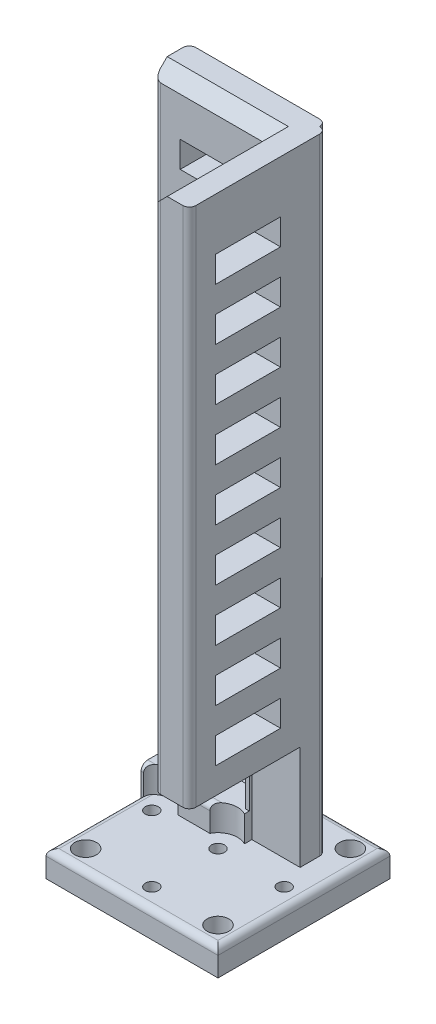
SolidWorks part; units mm, degrees
ref_plane "Front Plane" through (0, 0, 0) normal (0, 0, 1) x (1, 0, 0)
ref_plane "Top Plane" through (0, 0, 0) normal (0, 1, 0) x (1, 0, 0)
ref_plane "Right Plane" through (0, 0, 0) normal (1, 0, 0) x (0, 0, -1)
sketch "Sketch3" plane through (0, 0, 0) normal (0, 1, 0) x (1, 0, 0)
  line L0 (24, 0) -> (0, 0) construction
  line L1 (0, 0) -> (24, 0) construction
  line L2 (0, 0) -> (0, -36)
  line L3 (0, -36) -> (24, -36)
  line L4 (24, 0) -> (24, -36)
  line L5 (0, 0) -> (-36, 0)
  line L6 (24, 0) -> (24, 24)
  line L7 (24, 24) -> (-36, 24)
  line L8 (-36, 0) -> (-36, 24)
  dimension "D1" = 24
  dimension "D2" = 24
  dimension "D3" = 60
  dimension "D4" = 36
extrude "Boss-Extrude2" add sketch "Sketch3" along normal blind 250
sketch "Sketch4" plane through (0, 0, 0) normal (0, -1, 0) x (1, 0, 0)
  line L0 (-36, -24) -> (-36, 0) construction
  line L1 (0, 0) -> (-36, 0)
  line L2 (0, 0) -> (0, 36)
  line L3 (0, 36) -> (-36, 36)
  line L4 (-36, 0) -> (-36, 36)
  line L5 (-36, -24) -> (24, -24)
  line L6 (-36, -24) -> (-36, -40)
  line L7 (-36, -40) -> (40, -40)
  line L8 (40, -24) -> (40, -40)
  line L9 (24, 36) -> (40, 36)
  line L10 (24, 36) -> (24, -24)
  line L11 (24, -24) -> (40, -24) construction
  line L12 (40, 36) -> (40, -24)
  line L13 (0, 36) -> (24, 36) construction
  line L14 (24, -24) -> (40, -24) construction
  line L15 (-36, 18.4) -> (0, 18.4) construction
  line L16 (-18.4, 36) -> (-18.4, 0) construction
  line L17 (-36, -32.4) -> (40, -32.4) construction
  line L18 (32.4, 36) -> (32.4, -40) construction
  line L19 (-36, -7) -> (40, -7) construction
  line L20 (-18.4, 0) -> (-18.4, -40) construction
  line L21 (7, -40) -> (7, 36) construction
  circle A0 centre (-18.4, 18.4) radius 4.15
  circle A1 centre (-18.4, -32.4) radius 4.15
  circle A2 centre (32.4, 18.4) radius 4.15
  circle A3 centre (32.4, -32.4) radius 4.15
  circle A5 centre (-18.4, -7) radius 2.5
  circle A6 centre (32.4, -7) radius 2.5
  circle A7 centre (7, -32.4) radius 2.5
  dimension "D3" = 8.3
  dimension "D4" = 8.3
  dimension "D1" = 8.3
  dimension "D7" = 8.3
  dimension "D11" = 5
  dimension "D12" = 5
  dimension "D14" = 5
  dimension "D5" = 50.8
  dimension "D6" = 16
  dimension "D9" = 50.8
  dimension "D8" = 50.8
  dimension "D10" = 25.4
  dimension "D13" = 25.4
  dimension "D15" = 8.4
  dimension "D16" = 17.6
  dimension "D17" = 25.4
  dimension "D18" = 25.4
  dimension "D19" = 25.4
  dimension "D21" = 17.6
  dimension "D20" = 7.6
  dimension "D22" = 7.6
extrude "Boss-Extrude3" add sketch "Sketch4" against normal blind 10
sketch "Sketch5" plane through (0, 0, 0) normal (0, 0, 1) x (1, 0, 0)
  line L0 (-36, 250) -> (-36, 10) construction
  line L1 (-16, 30) -> (9, 30)
  line L2 (-16, 30) -> (-16, 20)
  line L3 (-16, 20) -> (9, 20)
  line L4 (9, 30) -> (9, 20)
  line L9 (-36, 10) -> (0, 10) construction
  line L10 (-16, 50) -> (-16, 40)
  line L11 (-16, 50) -> (9, 50)
  line L12 (9, 50) -> (9, 40)
  line L13 (-16, 40) -> (9, 40)
  line L14 (-16, 70) -> (-16, 60)
  line L15 (-16, 70) -> (9, 70)
  line L16 (9, 70) -> (9, 60)
  line L17 (-16, 60) -> (9, 60)
  line L18 (-16, 90) -> (-16, 80)
  line L19 (-16, 90) -> (9, 90)
  line L20 (9, 90) -> (9, 80)
  line L21 (-16, 80) -> (9, 80)
  line L22 (-16, 110) -> (-16, 100)
  line L23 (-16, 110) -> (9, 110)
  line L24 (9, 110) -> (9, 100)
  line L25 (-16, 100) -> (9, 100)
  line L26 (-16, 130) -> (-16, 120)
  line L27 (-16, 130) -> (9, 130)
  line L28 (9, 130) -> (9, 120)
  line L29 (-16, 120) -> (9, 120)
  line L30 (-16, 150) -> (-16, 140)
  line L31 (-16, 150) -> (9, 150)
  line L32 (9, 150) -> (9, 140)
  line L33 (-16, 140) -> (9, 140)
  line L34 (-16, 170) -> (-16, 160)
  line L35 (-16, 170) -> (9, 170)
  line L36 (9, 170) -> (9, 160)
  line L37 (-16, 160) -> (9, 160)
  line L38 (-16, 190) -> (-16, 180)
  line L39 (-16, 190) -> (9, 190)
  line L40 (9, 190) -> (9, 180)
  line L41 (-16, 180) -> (9, 180)
  line L42 (-16, 210) -> (-16, 200)
  line L43 (-16, 210) -> (9, 210)
  line L44 (9, 210) -> (9, 200)
  line L45 (-16, 200) -> (9, 200)
  line L46 (-16, 230) -> (-16, 220)
  line L47 (-16, 230) -> (9, 230)
  line L48 (9, 230) -> (9, 220)
  line L49 (-16, 220) -> (9, 220)
  dimension "D1" = 10
  dimension "D2" = 25
  dimension "D3" = 20
  dimension "D4" = 10
  dimension "D6" = 10
  dimension "D5" = 11
extrude "Cut-Extrude1" cut sketch "Sketch5" against normal up to surface (24 mm away) up to face at (-6, 130, -24)
sketch "Sketch6" plane through (0, 0, 0) normal (-1, 0, 0) x (0, 0, 1)
  line L0 (0, 10) -> (36, 10) construction
  line L1 (-9, 20) -> (16, 20)
  line L2 (-9, 20) -> (-9, 30)
  line L3 (-9, 30) -> (16, 30)
  line L4 (16, 20) -> (16, 30)
  line L5 (36, 250) -> (36, 10) construction
  line L38 (16, 40) -> (16, 50)
  line L39 (-9, 40) -> (-9, 50)
  line L40 (-9, 40) -> (16, 40)
  line L41 (-9, 50) -> (16, 50)
  line L42 (16, 60) -> (16, 70)
  line L43 (-9, 60) -> (-9, 70)
  line L44 (-9, 60) -> (16, 60)
  line L45 (-9, 70) -> (16, 70)
  line L46 (16, 80) -> (16, 90)
  line L47 (-9, 80) -> (-9, 90)
  line L48 (-9, 80) -> (16, 80)
  line L49 (-9, 90) -> (16, 90)
  line L50 (16, 100) -> (16, 110)
  line L51 (-9, 100) -> (-9, 110)
  line L52 (-9, 100) -> (16, 100)
  line L53 (-9, 110) -> (16, 110)
  line L54 (16, 120) -> (16, 130)
  line L55 (-9, 120) -> (-9, 130)
  line L56 (-9, 120) -> (16, 120)
  line L57 (-9, 130) -> (16, 130)
  line L58 (16, 140) -> (16, 150)
  line L59 (-9, 140) -> (-9, 150)
  line L60 (-9, 140) -> (16, 140)
  line L61 (-9, 150) -> (16, 150)
  line L62 (16, 160) -> (16, 170)
  line L63 (-9, 160) -> (-9, 170)
  line L64 (-9, 160) -> (16, 160)
  line L65 (-9, 170) -> (16, 170)
  line L66 (16, 180) -> (16, 190)
  line L67 (-9, 180) -> (-9, 190)
  line L68 (-9, 180) -> (16, 180)
  line L69 (-9, 190) -> (16, 190)
  line L70 (16, 200) -> (16, 210)
  line L71 (-9, 200) -> (-9, 210)
  line L72 (-9, 200) -> (16, 200)
  line L73 (-9, 210) -> (16, 210)
  line L74 (16, 220) -> (16, 230)
  line L75 (-9, 220) -> (-9, 230)
  line L76 (-9, 220) -> (16, 220)
  line L77 (-9, 230) -> (16, 230)
  dimension "D1" = 10
  dimension "D2" = 10
  dimension "D3" = 25
  dimension "D4" = 20
  dimension "D6" = 10
  dimension "D5" = 11
extrude "Cut-Extrude2" cut sketch "Sketch6" against normal up to surface (24 mm away) up to face at (24, 130, 6)
sketch "Sketch7" plane through (0, 250, 0) normal (0, 1, 0) x (1, 0, 0)
  line L0 (0, 0) -> (0, -36) construction
  line L1 (-36, 0) -> (0, 0)
  line L2 (-36, 0) -> (-36, 15.5)
  line L3 (-36, 15.5) -> (15.5, 15.5)
  line L4 (15.5, 0) -> (15.5, 15.5)
  line L5 (0, 0) -> (15.5, 0) construction
  line L6 (15.5, 0) -> (0, 0) construction
  line L7 (15.5, 0) -> (15.5, -36)
  line L8 (15.5, -36) -> (0, -36)
  line L9 (0, 0) -> (0, -36)
  dimension "D1" = 15.5
  dimension "D2" = 15.5
extrude "Cut-Extrude3" cut sketch "Sketch7" against normal up to surface (240 mm away) up to face at (-18.4, 10, 14.25)
sketch "Sketch8" plane through (0, 10, 0) normal (0, 1, 0) x (1, 0, 0)
  line L0 (14, 24) -> (14, 29)
  line L1 (24, 24) -> (-36, 24) construction
  line L2 (14, 29) -> (26.5, 29)
  line L3 (29, 26.5) -> (29, 14)
  line L4 (29, 14) -> (24, 14)
  line L5 (24, -36) -> (24, 24) construction
  line L6 (24, 14) -> (24, 24)
  line L7 (24, 24) -> (-36, 24) construction
  line L8 (24, 24) -> (14, 24)
  line L9 (26.5, 29) -> (29, 29) construction
  line L10 (29, 29) -> (26.5, 29) construction
  line L11 (29, 29) -> (29, 26.5) construction
  line L12 (29, 26.5) -> (26.5, 26.5)
  line L13 (26.5, 29) -> (26.5, 26.5)
  line L14 (29, 29) -> (29, 26.5) construction
  dimension "D1" = 5
  dimension "D2" = 5
  dimension "D3" = 10
  dimension "D4" = 10
  dimension "D5" = 2.5
  dimension "D6" = 2.5
extrude "Boss-Extrude4" add sketch "Sketch8" along normal up to surface (240 mm away) up to face at (1.1667, 250, -1.1667)
ref_plane "Plane1" through (0, 40, 0) normal (0, 1, 0) x (1, 0, 0)
sketch "Sketch10" plane through (24, 0, 0) normal (1, 0, 0) x (0, 0, -1)
  line L0 (-36, 250) -> (14, 250)
  line L1 (14, 250) -> (14, 20)
  line L2 (14, 10) -> (-36, 10) construction
  line L3 (-36, 20) -> (-36, 250)
  line L4 (9, 30) -> (-16, 30)
  line L5 (9, 20) -> (9, 30)
  line L6 (-16, 20) -> (9, 20)
  line L7 (-16, 30) -> (-16, 20)
  line L8 (9, 30) -> (-16, 30)
  line L9 (9, 20) -> (9, 30)
  line L11 (-16, 30) -> (-16, 20)
  line L12 (9, 40) -> (9, 50)
  line L13 (-16, 40) -> (9, 40)
  line L14 (-16, 50) -> (-16, 40)
  line L15 (9, 50) -> (-16, 50)
  line L16 (9, 40) -> (9, 50)
  line L17 (-16, 40) -> (9, 40)
  line L18 (-16, 50) -> (-16, 40)
  line L19 (9, 50) -> (-16, 50)
  line L20 (9, 60) -> (9, 70)
  line L21 (-16, 60) -> (9, 60)
  line L22 (-16, 70) -> (-16, 60)
  line L23 (9, 70) -> (-16, 70)
  line L24 (9, 60) -> (9, 70)
  line L25 (-16, 60) -> (9, 60)
  line L26 (-16, 70) -> (-16, 60)
  line L27 (9, 70) -> (-16, 70)
  line L28 (9, 120) -> (9, 130)
  line L29 (-16, 120) -> (9, 120)
  line L30 (-16, 130) -> (-16, 120)
  line L31 (9, 130) -> (-16, 130)
  line L32 (9, 120) -> (9, 130)
  line L33 (-16, 120) -> (9, 120)
  line L34 (-16, 130) -> (-16, 120)
  line L35 (9, 130) -> (-16, 130)
  line L36 (9, 100) -> (9, 110)
  line L37 (-16, 100) -> (9, 100)
  line L38 (-16, 110) -> (-16, 100)
  line L39 (9, 110) -> (-16, 110)
  line L40 (9, 100) -> (9, 110)
  line L41 (-16, 100) -> (9, 100)
  line L42 (-16, 110) -> (-16, 100)
  line L43 (9, 110) -> (-16, 110)
  line L44 (9, 80) -> (9, 90)
  line L45 (-16, 80) -> (9, 80)
  line L46 (-16, 90) -> (-16, 80)
  line L47 (9, 90) -> (-16, 90)
  line L48 (9, 80) -> (9, 90)
  line L49 (-16, 80) -> (9, 80)
  line L50 (-16, 90) -> (-16, 80)
  line L51 (9, 90) -> (-16, 90)
  line L52 (9, 220) -> (9, 230)
  line L53 (-16, 220) -> (9, 220)
  line L54 (-16, 230) -> (-16, 220)
  line L55 (9, 230) -> (-16, 230)
  line L56 (9, 220) -> (9, 230)
  line L57 (-16, 220) -> (9, 220)
  line L58 (-16, 230) -> (-16, 220)
  line L59 (9, 230) -> (-16, 230)
  line L60 (9, 200) -> (9, 210)
  line L61 (-16, 200) -> (9, 200)
  line L62 (-16, 210) -> (-16, 200)
  line L63 (9, 210) -> (-16, 210)
  line L64 (9, 200) -> (9, 210)
  line L65 (-16, 200) -> (9, 200)
  line L66 (-16, 210) -> (-16, 200)
  line L67 (9, 210) -> (-16, 210)
  line L68 (9, 180) -> (9, 190)
  line L69 (-16, 180) -> (9, 180)
  line L70 (-16, 190) -> (-16, 180)
  line L71 (9, 190) -> (-16, 190)
  line L72 (9, 180) -> (9, 190)
  line L73 (-16, 180) -> (9, 180)
  line L74 (-16, 190) -> (-16, 180)
  line L75 (9, 190) -> (-16, 190)
  line L76 (9, 160) -> (9, 170)
  line L77 (-16, 160) -> (9, 160)
  line L78 (-16, 170) -> (-16, 160)
  line L79 (9, 170) -> (-16, 170)
  line L80 (9, 160) -> (9, 170)
  line L81 (-16, 160) -> (9, 160)
  line L82 (-16, 170) -> (-16, 160)
  line L83 (9, 170) -> (-16, 170)
  line L84 (9, 140) -> (9, 150)
  line L85 (-16, 140) -> (9, 140)
  line L86 (-16, 150) -> (-16, 140)
  line L87 (9, 150) -> (-16, 150)
  line L88 (9, 140) -> (9, 150)
  line L89 (-16, 140) -> (9, 140)
  line L90 (-16, 150) -> (-16, 140)
  line L91 (9, 150) -> (-16, 150)
  line L92 (-16, 20) -> (-36, 20)
  line L93 (9, 20) -> (14, 20)
  line L94 (-36, 10) -> (-36, 20) construction
  line L95 (14, 20) -> (14, 10) construction
  dimension "D1" = 0
  dimension "D2" = 0
  dimension "D3" = 0
  dimension "D4" = 0
  dimension "D5" = 0
  dimension "D6" = 0
  dimension "D7" = 0
  dimension "D8" = 0
  dimension "D9" = 0
  dimension "D10" = 0
  dimension "D11" = 0
extrude "Boss-Extrude8" add sketch "Sketch10" along normal blind 5
sketch "Sketch11" plane through (0, 0, -24) normal (0, 0, -1) x (-1, 0, 0)
  line L0 (-9, 20) -> (-14, 20)
  line L1 (-14, 250) -> (-14, 10) construction
  line L2 (16, 20) -> (36, 20)
  line L3 (36, 250) -> (36, 10) construction
  line L4 (-9, 230) -> (-9, 220)
  line L5 (16, 230) -> (-9, 230)
  line L6 (16, 220) -> (16, 230)
  line L7 (-9, 220) -> (16, 220)
  line L8 (-9, 230) -> (-9, 220)
  line L9 (16, 230) -> (-9, 230)
  line L10 (16, 220) -> (16, 230)
  line L11 (-9, 220) -> (16, 220)
  line L12 (-9, 210) -> (-9, 200)
  line L13 (16, 210) -> (-9, 210)
  line L14 (16, 200) -> (16, 210)
  line L15 (-9, 200) -> (16, 200)
  line L16 (-9, 210) -> (-9, 200)
  line L17 (16, 210) -> (-9, 210)
  line L18 (16, 200) -> (16, 210)
  line L19 (-9, 200) -> (16, 200)
  line L20 (-9, 190) -> (-9, 180)
  line L21 (16, 190) -> (-9, 190)
  line L22 (16, 180) -> (16, 190)
  line L23 (-9, 180) -> (16, 180)
  line L24 (-9, 190) -> (-9, 180)
  line L25 (16, 190) -> (-9, 190)
  line L26 (16, 180) -> (16, 190)
  line L27 (-9, 180) -> (16, 180)
  line L28 (-9, 170) -> (-9, 160)
  line L29 (16, 170) -> (-9, 170)
  line L30 (16, 160) -> (16, 170)
  line L31 (-9, 160) -> (16, 160)
  line L32 (-9, 170) -> (-9, 160)
  line L33 (16, 170) -> (-9, 170)
  line L34 (16, 160) -> (16, 170)
  line L35 (-9, 160) -> (16, 160)
  line L36 (-9, 150) -> (-9, 140)
  line L37 (16, 150) -> (-9, 150)
  line L38 (16, 140) -> (16, 150)
  line L39 (-9, 140) -> (16, 140)
  line L40 (-9, 150) -> (-9, 140)
  line L41 (16, 150) -> (-9, 150)
  line L42 (16, 140) -> (16, 150)
  line L43 (-9, 140) -> (16, 140)
  line L44 (-9, 130) -> (-9, 120)
  line L45 (16, 130) -> (-9, 130)
  line L46 (16, 120) -> (16, 130)
  line L47 (-9, 120) -> (16, 120)
  line L48 (-9, 130) -> (-9, 120)
  line L49 (16, 130) -> (-9, 130)
  line L50 (16, 120) -> (16, 130)
  line L51 (-9, 120) -> (16, 120)
  line L52 (-9, 110) -> (-9, 100)
  line L53 (16, 110) -> (-9, 110)
  line L54 (16, 100) -> (16, 110)
  line L55 (-9, 100) -> (16, 100)
  line L56 (-9, 110) -> (-9, 100)
  line L57 (16, 110) -> (-9, 110)
  line L58 (16, 100) -> (16, 110)
  line L59 (-9, 100) -> (16, 100)
  line L60 (-9, 90) -> (-9, 80)
  line L61 (16, 90) -> (-9, 90)
  line L62 (16, 80) -> (16, 90)
  line L63 (-9, 80) -> (16, 80)
  line L64 (-9, 90) -> (-9, 80)
  line L65 (16, 90) -> (-9, 90)
  line L66 (16, 80) -> (16, 90)
  line L67 (-9, 80) -> (16, 80)
  line L68 (-9, 70) -> (-9, 60)
  line L69 (16, 70) -> (-9, 70)
  line L70 (16, 60) -> (16, 70)
  line L71 (-9, 60) -> (16, 60)
  line L72 (-9, 70) -> (-9, 60)
  line L73 (16, 70) -> (-9, 70)
  line L74 (16, 60) -> (16, 70)
  line L75 (-9, 60) -> (16, 60)
  line L76 (-9, 50) -> (-9, 40)
  line L77 (16, 50) -> (-9, 50)
  line L78 (16, 40) -> (16, 50)
  line L79 (-9, 40) -> (16, 40)
  line L80 (-9, 50) -> (-9, 40)
  line L81 (16, 50) -> (-9, 50)
  line L82 (16, 40) -> (16, 50)
  line L83 (-9, 40) -> (16, 40)
  line L84 (16, 30) -> (-9, 30)
  line L85 (16, 20) -> (16, 30)
  line L86 (-9, 20) -> (16, 20)
  line L87 (-9, 30) -> (-9, 20)
  line L88 (16, 30) -> (-9, 30)
  line L89 (16, 20) -> (16, 30)
  line L90 (-9, 20) -> (16, 20) construction
  line L91 (-9, 30) -> (-9, 20)
  line L92 (36, 20) -> (36, 250)
  line L93 (36, 250) -> (-14, 250)
  line L94 (-14, 250) -> (-14, 20)
  dimension "D1" = 0
  dimension "D2" = 0
  dimension "D3" = 0
  dimension "D4" = 0
  dimension "D5" = 0
  dimension "D6" = 0
  dimension "D7" = 0
  dimension "D8" = 0
  dimension "D9" = 0
  dimension "D10" = 0
  dimension "D11" = 0
extrude "Boss-Extrude9" add sketch "Sketch11" along normal blind 5
sketch "Sketch12" plane through (0, 10, 0) normal (0, 1, 0) x (1, 0, 0)
  line L0 (-36, -36) -> (-36, 15.5) construction
  line L1 (-36, 10.5) -> (10.5, 10.5)
  line L2 (-36, 10.5) -> (-36, 15.5)
  line L3 (-36, 15.5) -> (15.5, 15.5)
  line L4 (15.5, 10.5) -> (15.5, 15.5)
  line L5 (15.5, -36) -> (-36, -36) construction
  line L6 (10.5, -36) -> (15.5, -36)
  line L7 (10.5, -36) -> (10.5, 10.5)
  line L8 (10.5, 10.5) -> (15.5, 10.5) construction
  line L9 (15.5, -36) -> (15.5, 10.5)
  line L10 (10.5, 10.5) -> (15.5, 10.5) construction
  dimension "D1" = 5
  dimension "D2" = 5
extrude "Boss-Extrude10" add sketch "Sketch12" along normal up to surface (10 mm away) up to face at (-3.5, 20, -19.75)
sketch "Sketch13" plane through (0, 0, 0) normal (0, -1, 0) x (1, 0, 0)
  line L0 (-36, 18.4) -> (40, 18.4) construction
  line L1 (-36, -40) -> (-36, 36) construction
  line L2 (40, -40) -> (40, 36) construction
  line L3 (-18.4, -40) -> (-18.4, 36) construction
  line L4 (-36, -40) -> (40, -40) construction
  line L5 (-36, 36) -> (40, 36) construction
  circle A0 centre (7, 18.4) radius 2.5
  circle A1 centre (32.4, -7) radius 2.5 construction
  circle A3 centre (-18.4, -7) radius 2.5
  circle A4 centre (-18.4, -32.4) radius 4.15 construction
  circle A5 centre (7, -32.4) radius 2.5 construction
  circle A6 centre (7, -7) radius 2.5
  dimension "D1" = 25.4
  dimension "D2" = 25.4
  dimension "D3" = 25.4
  dimension "D4" = 25.4
  dimension "D5" = 25.4
  dimension "D6" = 25.4
extrude "Cut-Extrude4" cut sketch "Sketch13" against normal up to surface (20 mm away) up to face at (3.2143, 20, -3.2143)
sketch "Sketch14" plane through (0, 20, 0) normal (0, 1, 0) x (1, 0, 0)
  circle A0 centre (-18.4, 7) radius 7.5
  circle A1 centre (7, 7) radius 7.5
  circle A2 centre (7, -18.4) radius 7.5
  dimension "D1" = 15
extrude "Cut-Extrude5" cut sketch "Sketch14" against normal up to surface (10 mm away) up to face at (7, 10, 15.9)
sketch "Sketch15" plane through (0, 250, 0) normal (0, 1, 0) x (1, 0, 0)
  line L0 (10.5, -36) -> (-36, -36) construction
  line L1 (-36, 40) -> (-26, 40)
  line L2 (-36, 40) -> (-36, -36)
  line L3 (-36, -36) -> (-26, -36)
  line L4 (-26, 40) -> (-26, -26)
  line L5 (-26, -26) -> (-26, -36) construction
  line L6 (40, -36) -> (-26, -36)
  line L7 (40, -36) -> (40, -26)
  line L8 (40, -26) -> (-26, -26)
  line L9 (-26, -36) -> (-26, -26) construction
  dimension "D1" = 10
  dimension "D2" = 10
extrude "Cut-Extrude6" cut sketch "Sketch15" against normal up to surface (250 mm away) up to face at (7, 0, 15.9)
chamfer "Chamfer3" distance 5 angle 45 2 edges at (15.5, 250, 5.25) (-5.25, 250, -15.5)
fillet "Fillet1" radius 2.5 24 edges at (40, 10, -7) (7, 10, -40) (10.5, 20, 25.5166) (-21, 20, -29) (11.5, 20, -29) (29, 20, -11.5) (29, 20, 21) (26.5, 130, -29) (29, 130, -26.5) (10.5, 20, 5.7) (-5.7, 20, -10.5) (-25.5166, 20, -10.5) (14, 15, -29) (29, 15, -14) (15.5, 132.5, 26) (29, 135, 26) (24, 15, 26) (-26, 15, -24) (-26, 135, -29) (-26, 132.5, -15.5) (-26, 10, -32) (32, 10, 26) (-7.75, 10, 26) (-26, 10, 7.75)
sketch "Sketch16" plane through (29, 0, 0) normal (1, 0, 0) x (0, 0, -1)
  line L0 (16.5, 22.5) -> (16.5, 10) construction
  line L1 (16.5, 10) -> (-26, 10)
  line L2 (16.5, 10) -> (16.5, 50)
  line L3 (16.5, 50) -> (-26, 50)
  line L4 (-26, 10) -> (-26, 50)
  line L5 (-26, 20) -> (-26, 250) construction
  line L7 (9, 50) -> (-16, 50) construction
  line L8 (-23.5, 10) -> (14, 10) construction
extrude "Cut-Extrude7" cut sketch "Sketch16" against normal up to surface (18.5 mm away) up to face at (10.5, 13.75, 5.7)
sketch "Sketch18" plane through (0, 20, 0) normal (0, -1, 0) x (1, 0, 0)
  line L0 (-26, -18) -> (-26, -13) construction
  line L1 (-16, -24) -> (-26, -24)
  line L2 (-16, -24) -> (-16, -29)
  line L3 (-16, -29) -> (-26, -29)
  line L4 (-26, -24) -> (-26, -29)
  line L6 (-16, -29) -> (-23.5, -29) construction
  line L7 (-16, -24) -> (-23.5, -24) construction
  dimension "D1" = 10
extrude "Cut-Extrude9" cut sketch "Sketch18" against normal blind 30
fillet "Fillet2" radius 2.5 2 edges at (-26, 35, -24) (-16, 35, -29)
sketch "Sketch19" plane through (10.5, 0, 0) normal (-1, 0, 0) x (0, 0, 1)
  line L0 (23.5, 10) -> (27.3342, 10)
  line L1 (27.3342, 10) -> (27.3342, 7.5)
  line L2 (27.3342, 7.5) -> (26, 7.5)
  arc A0 (25.0332, 9.4746) -> (23.5, 10) centre (23.5, 7.5) ccw construction
  arc A1 (26, 7.5) -> (25.0332, 9.4746) centre (23.5, 7.5) ccw construction
  arc A2 (25.0332, 9.4746) -> (23.5, 10) centre (23.5, 7.5) ccw
  arc A3 (26, 7.5) -> (25.0332, 9.4746) centre (23.5, 7.5) ccw
extrude "Cut-Extrude10" cut sketch "Sketch19" against normal up to surface (29.5 mm away) up to face at (40, 3.75, -7)
equation "\"D2@Sketch3\"=\"D1@Sketch3\""
equation "\"D4@Sketch3\"=\"D3@Sketch3\"-\"D2@Sketch3\""
equation "\"D4@Sketch4\"=\"D3@Sketch4\""
equation "\"D1@Sketch4\"=\"D3@Sketch4\""
equation "\"D2@Sketch7\"=\"D1@Sketch7\""
equation "\"D12@Sketch4\"=\"D11@Sketch4\""
equation "\"D14@Sketch4\"=\"D11@Sketch4\""
equation "\"D7@Sketch4\"=\"D3@Sketch4\""
equation "\"D5@Sketch13\"=\"D4@Sketch13\""
equation "\"D6@Sketch13\"=\"D4@Sketch13\""
equation "\"D2@Sketch13\"=\"D4@Sketch13\""
equation "\"D1@Sketch13\"=\"D4@Sketch13\""
equation "\"D3@Sketch13\"=\"D4@Sketch13\""
